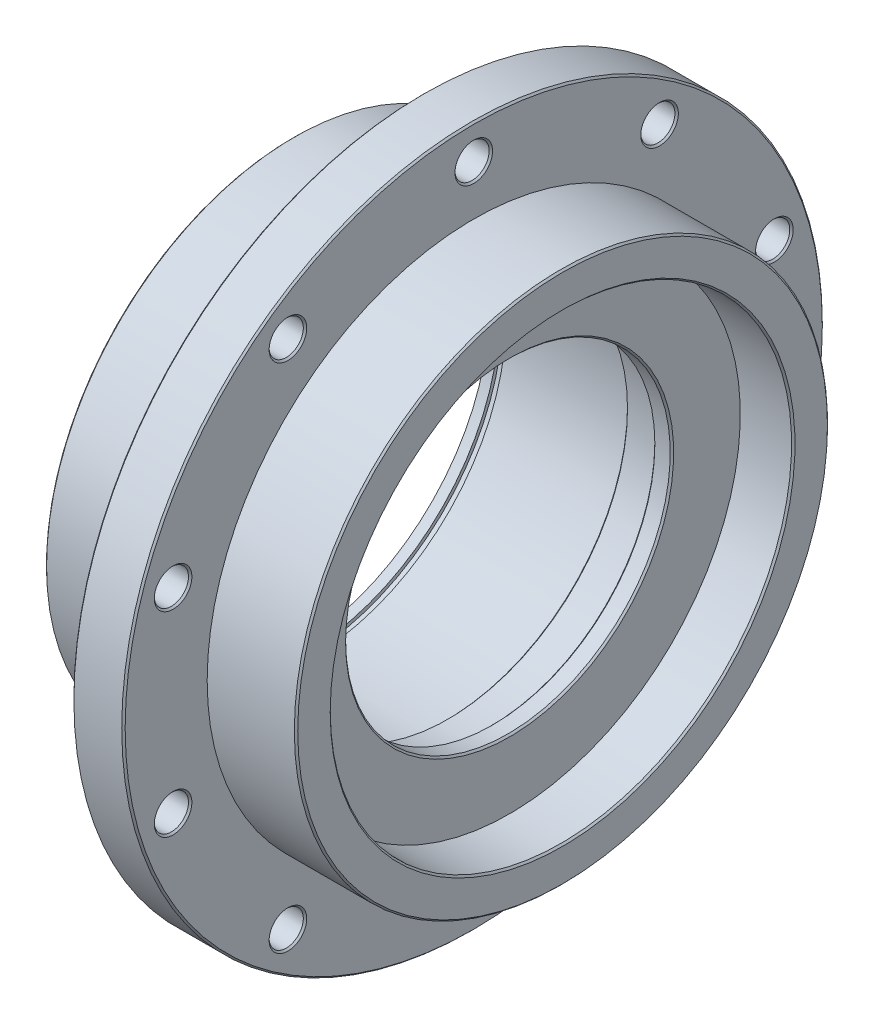
SolidWorks part; units mm, degrees
ref_plane "前视基准面" through (0, 0, 0) normal (0, 0, 1) x (1, 0, 0)
ref_plane "上视基准面" through (0, 0, 0) normal (0, 1, 0) x (1, 0, 0)
ref_plane "右视基准面" through (0, 0, 0) normal (1, 0, 0) x (0, 0, -1)
other "Configuration Table"
sketch "草图1" plane through (0, 0, 0) normal (0, 0, 1) x (1, 0, 0)
  line L0 (0, 0) -> (248.0835, 0) construction
  line L1 (0, 57.5) -> (0, 72.5)
  line L2 (0, 72.5) -> (38, 72.5)
  line L3 (38, 72.5) -> (38, 102.5)
  line L4 (38, 102.5) -> (53, 102.5)
  line L5 (53, 102.5) -> (53, 78)
  line L6 (53, 78) -> (79, 78)
  line L7 (79, 78) -> (79, 67.5)
  line L8 (79, 67.5) -> (63.5, 67.5)
  line L9 (63.5, 67.5) -> (63.5, 47.5)
  line L10 (63.5, 47.5) -> (58, 47.5)
  line L11 (58, 47.5) -> (58, 52.5)
  line L12 (58, 52.5) -> (45, 52.5)
  line L13 (45, 52.5) -> (45, 57.5)
  line L16 (45, 57.5) -> (5, 57.5)
  line L17 (5, 57.5) -> (5, 58.5)
  line L18 (5, 58.5) -> (3, 58.5)
  line L19 (3, 58.5) -> (3, 57.5)
  line L20 (3, 57.5) -> (0, 57.5)
  dimension "D1" = 115
  dimension "D2" = 117
  dimension "D3" = 145
  dimension "D4" = 205
  dimension "D5" = 156
  dimension "D6" = 135
  dimension "D7" = 95
  dimension "D8" = 3
  dimension "D9" = 2
  dimension "D10" = 45
  dimension "D11" = 58
  dimension "D12" = 15.5
  dimension "D13" = 63.5
  dimension "D14" = 38
  dimension "D15" = 26
  dimension "D16" = 105
revolve "旋转1" add sketch "草图1" angle 360 about L0
sketch "草图3" plane through (38, 0, 0) normal (-1, 0, 0) x (0, 0, 1)
  circle A0 centre (0, 0) radius 92.5 construction
  circle A1 centre (0, 92.5) radius 5
  circle A2 centre (54.3701, 74.8341) radius 5
  circle A3 centre (87.9727, 28.5841) radius 5
  circle A4 centre (87.9727, -28.5841) radius 5
  circle A5 centre (54.3701, -74.8341) radius 5
  circle A6 centre (0, -92.5) radius 5
  circle A7 centre (-54.3701, -74.8341) radius 5
  circle A8 centre (-87.9727, -28.5841) radius 5
  circle A9 centre (-87.9727, 28.5841) radius 5
  circle A10 centre (-54.3701, 74.8341) radius 5
  point P25 (0, 0)
  dimension "D1" = 185
  dimension "D2" = 10
  dimension "D3" = 10
extrude "切除-拉伸2" cut sketch "草图3" against normal through all
sketch "草图4" plane through (0, 0, 0) normal (-1, 0, 0) x (0, 0, 1)
  line L0 (0, 0) -> (0, 65) construction
  circle A0 centre (0, 0) radius 65 construction
  dimension "D1" = 130
hole_wizard "Ø5.0 (5) 直径孔1" positions "3D草图1" profile "草图5" hole size "Ø5.0" standard "GB"
sketch3d "3D草图1"
  point P0 (0, 65, 0)
sketch "草图5" plane through (0, 65, 0) normal (0, 1, 0) x (0, 0, 1)
  line L0 (0, 0) -> (0, 16.5022)
  line L1 (0, 16.5022) -> (2.5, 15)
  line L2 (2.5, 15) -> (2.5, 0)
  line L5 (2.5, 0) -> (0, 0)
  line L10 (0, 16.5022) -> (-2.5, 15) construction
  line L11 (0, -6.35) -> (0, 107.95) construction
  dimension "孔直径" = 5
  dimension "孔深度" = 15
  dimension "导头角度" = 118
pattern_circular "阵列(圆周)1" count 4 over 360 about axis through (0, 0, 0) along (-1, 0, 0) of "Ø5.0 (5) 直径孔1" reverse direction yes
chamfer "倒角1" distance 0.5 angle 45 8 edges at (0, 0, 72.5) (38, 0, 102.5) (53, 0, 102.5) (79, 0, 78) (45, 0, 52.5) (58, 0, 47.5) (63.5, 0, 47.5) (79, 0, 67.5)
chamfer "倒角2" distance 0.5 angle 45 24 edges at (0, -65, 2.5) (0, 0, 67.5) (0, 65, 2.5) (0, 0, -62.5) (53, 74.8341, 59.3701) (53, 28.5841, 92.9727) (53, -28.5841, 92.9727) (53, -74.8341, 59.3701) (53, -92.5, 5) (53, -74.8341, -49.3701) (53, -28.5841, -82.9727) (53, 28.5841, -82.9727) (53, 74.8341, -49.3701) (53, 92.5, 5) (38, 92.5, 5) (38, 74.8341, 59.3701) (38, 28.5841, 92.9727) (38, -28.5841, 92.9727) (38, -74.8341, 59.3701) (38, -92.5, 5) (38, -74.8341, -49.3701) (38, -28.5841, -82.9727) (38, 28.5841, -82.9727) (38, 74.8341, -49.3701)
